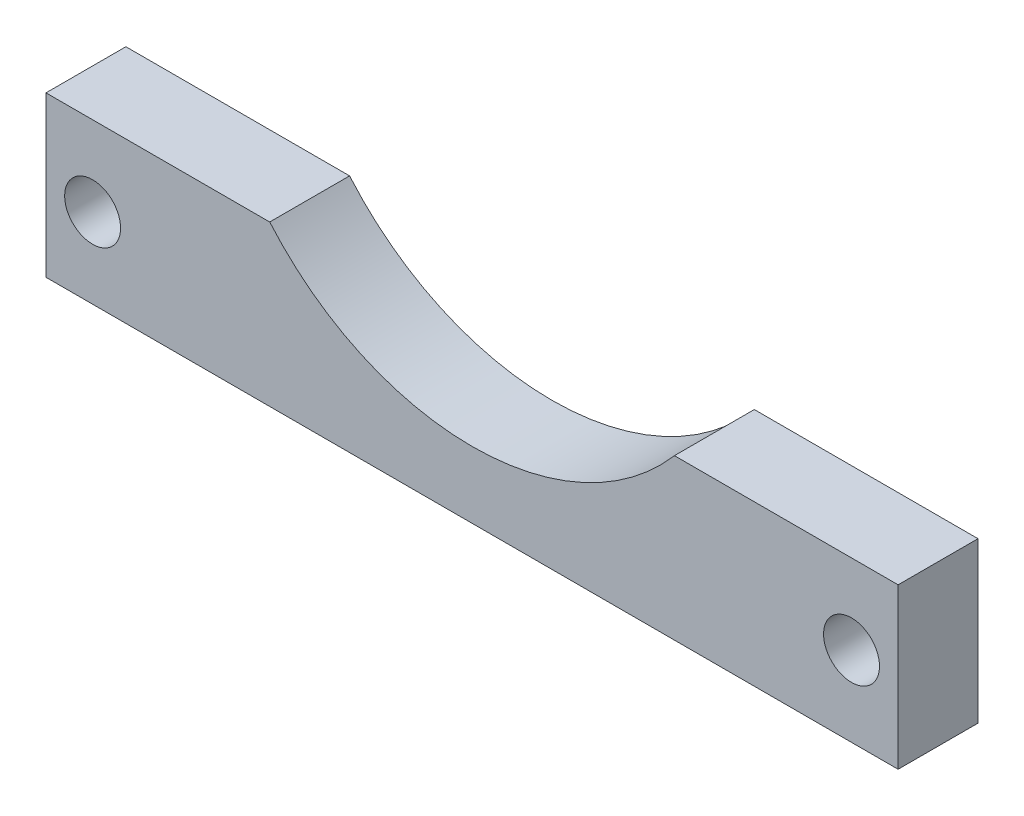
SolidWorks part; units mm, degrees
ref_plane "Plan de face" through (0, 0, 0) normal (0, 0, 1) x (1, 0, 0)
ref_plane "Plan de dessus" through (0, 0, 0) normal (0, 1, 0) x (1, 0, 0)
ref_plane "Plan de droite" through (0, 0, 0) normal (1, 0, 0) x (0, 0, -1)
sketch "Esquisse1" plane through (0, 0, 0) normal (0, 0, 1) x (1, 0, 0)
  line L0 (-7.6048, 5.7039) -> (-7.6048, -0.2961) construction
  line L1 (-23.6048, 5.7039) -> (8.3952, 5.7039)
  line L2 (-23.6048, 5.7039) -> (-23.6048, -0.2961)
  line L3 (-23.6048, -0.2961) -> (8.3952, -0.2961)
  line L4 (8.3952, 5.7039) -> (8.3952, -0.2961)
  line L5 (-23.6048, 5.7039) -> (8.3952, -0.2961) construction
  line L6 (-23.6048, -0.2961) -> (8.3952, 5.7039) construction
  line L7 (-7.6048, -0.2961) -> (-7.6048, 24.7039) construction
  circle A0 centre (6.6452, 2.7039) radius 1.05
  circle A1 centre (-21.8548, 2.7039) radius 1.05
  circle A2 centre (-7.6048, 12.2039) radius 10
  dimension "D3" = 14.25
  dimension "D5" = 20
  dimension "D7" = 2.1
  dimension "D1" = 32
  dimension "D2" = 6
  dimension "D4" = 3
  dimension "D6" = 12.5
extrude "Boss.-Extru.1" add sketch "Esquisse1" along normal blind 3 contours L1 L4 L3 L2
extrude "Enlèv. mat.-Extru.1" cut sketch "Esquisse1<3>" along normal blind 19 contours L1 A2 | A0 | A1 region at (-7.6048, 4.2805, 0)
sketch "Esquisse1<3>" plane through (0, 0, 0) normal (0, 0, 1) x (1, 0, 0) same geometry as "Esquisse1"
